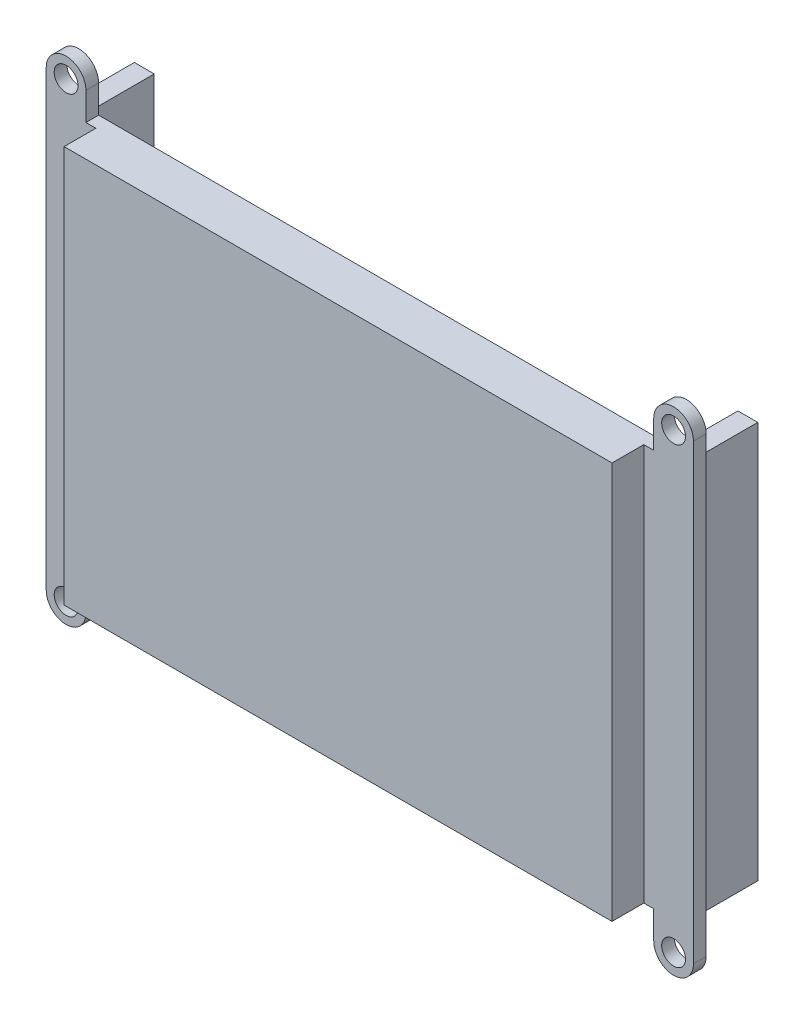
SolidWorks part; units mm, degrees
ref_plane "Vehicle Ground Plane" through (0, 0, 0) normal (0, 0, 1) x (1, 0, 0)
ref_plane "Vehicle Centreline Plane" through (0, 0, 0) normal (0, 1, 0) x (1, 0, 0)
ref_plane "Roll Hoop Plane" through (0, 0, 0) normal (1, 0, 0) x (0, 0, -1)
ref_axis "X-Axis" through (-88.99, 0, 0) along (1, 0, 0)
ref_axis "Y-Axis" through (0, 55, 0) along (0, -1, 0)
ref_axis "Z-Axis" through (0, 0, -88.99) along (0, 0, 1)
sketch "Sketch1" plane through (0, 0, 0) normal (0, 0, 1) x (1, 0, 0)
  line L1 (-34.5, -25) -> (34.5, -25)
  line L2 (-34.5, -25) -> (-34.5, 25)
  line L3 (-34.5, 25) -> (34.5, 25)
  line L4 (34.5, -25) -> (34.5, 25)
  line L5 (-34.5, -25) -> (34.5, 25) construction
  line L6 (-34.5, 25) -> (34.5, -25) construction
  point P0 (0, 0)
  dimension "D1" = 69
  dimension "D2" = 50
extrude "Boss-Extrude1" add sketch "Sketch1" along normal blind 4
sketch "Sketch2" plane through (0, 0, 0) normal (0, 0, -1) x (-1, 0, 0)
  line L1 (-40.75, -25) -> (40.75, -25)
  line L2 (-40.75, -25) -> (-40.75, 25)
  line L3 (-40.75, 25) -> (40.75, 25)
  line L4 (40.75, -25) -> (40.75, 25)
  line L5 (-40.75, -25) -> (40.75, 25) construction
  line L6 (-40.75, 25) -> (40.75, -25) construction
  point P0 (0, 0)
  dimension "D1" = 50
  dimension "D2" = 81.5
extrude "Boss-Extrude2" add sketch "Sketch2" along normal blind 1.6
sketch "Sketch4" plane through (0, 0, 0) normal (0, 0, 1) x (1, 0, 0)
  line L0 (-40.75, 25) -> (-34.5, 25) construction
  line L1 (-40.75, -25) -> (-40.75, 25) construction
  line L2 (-40.75, 28.5) -> (-40.75, 25)
  line L3 (-40.75, 25) -> (-35.75, 25)
  line L4 (-35.75, 25) -> (-35.75, 28.5)
  line L5 (-40.75, 25) -> (40.75, 25) construction
  line L6 (3.08, 0) -> (-3.08, 0) construction
  line L7 (-35.75, -25) -> (-35.75, -28.5)
  line L8 (-40.75, -25) -> (-35.75, -25)
  line L9 (-40.75, -28.5) -> (-40.75, -25)
  line L10 (0, -3.08) -> (0, 3.08) construction
  line L11 (40.75, -28.5) -> (40.75, -25)
  line L12 (40.75, -25) -> (35.75, -25)
  line L13 (35.75, -25) -> (35.75, -28.5)
  line L14 (35.75, 25) -> (35.75, 28.5)
  line L15 (40.75, 25) -> (35.75, 25)
  line L16 (40.75, 28.5) -> (40.75, 25)
  circle A1 centre (-38.25, 28.5) radius 1.5
  arc A2 (-35.75, 28.5) -> (-40.75, 28.5) centre (-38.25, 28.5) ccw
  arc A3 (-35.75, -28.5) -> (-40.75, -28.5) centre (-38.25, -28.5) cw
  circle A4 centre (-38.25, -28.5) radius 1.5
  circle A5 centre (38.25, -28.5) radius 1.5
  arc A6 (35.75, -28.5) -> (40.75, -28.5) centre (38.25, -28.5) ccw
  arc A7 (35.75, 28.5) -> (40.75, 28.5) centre (38.25, 28.5) cw
  circle A8 centre (38.25, 28.5) radius 1.5
  dimension "D3" = 5
  dimension "D4" = 3
  dimension "D1" = 3.5
  dimension "D2" = 2.5
extrude "Boss-Extrude3" add sketch "Sketch4" against normal blind 1.6 separate body
sketch "Sketch5" plane through (0, 0, -1.6) normal (0, 0, -1) x (-1, 0, 0)
  line L0 (-40.75, 25) -> (-40.75, -25) construction
  line L1 (-39.25, 25) -> (-36.75, 25)
  line L2 (-39.25, 25) -> (-39.25, -25)
  line L3 (-39.25, -25) -> (-36.75, -25)
  line L4 (-36.75, 25) -> (-36.75, -25)
  line L6 (3.08, 0) -> (-3.08, 0) construction
  line L7 (0, 3.08) -> (0, -3.08) construction
  line L8 (36.75, 25) -> (36.75, -25)
  line L9 (39.25, -25) -> (36.75, -25)
  line L10 (39.25, 25) -> (39.25, -25)
  line L11 (39.25, 25) -> (36.75, 25)
  point P6 (-39.25, 0)
  dimension "D1" = 1.5
  dimension "D2" = 2.5
  dimension "D3" = 50
extrude "Boss-Extrude4" add sketch "Sketch5" along normal blind 8
